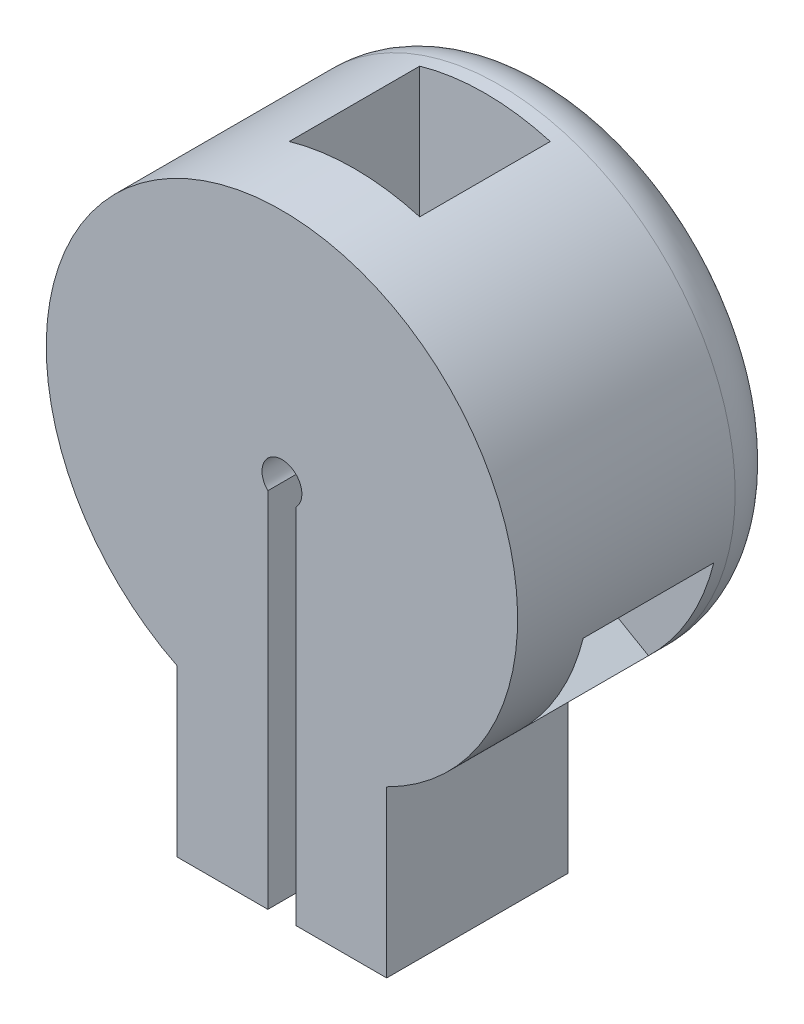
SolidWorks part; units mm, degrees
note: '?' marks a value the reader was unsure of. The reader was unsure of these and kept them because the rebuilt part matched: shared geometry of "Sketch1<4>".
ref_plane "Front Plane" through (0, 0, 0) normal (0, 0, 1) x (1, 0, 0)
ref_plane "Top Plane" through (0, 0, 0) normal (0, 1, 0) x (1, 0, 0)
ref_plane "Right Plane" through (0, 0, 0) normal (1, 0, 0) x (0, 0, -1)
sketch "Sketch1" plane through (0, 0, 0) normal (0, 0, 1) x (1, 0, 0)
  line L0 (-1.1, 0) -> (1.1, 0) construction
  line L1 (-0.7778, -20.7778) -> (-5.7778, -20.7778)
  line L2 (0, 0) -> (-0.7778, -0.7778) construction
  line L3 (-5.7778, -20.7778) -> (-5.7778, -11.6455)
  line L4 (0.7778, -20.7778) -> (5.7778, -20.7778)
  line L5 (5.7778, -20.7778) -> (5.7778, -11.6455)
  line L6 (0, 0) -> (0.7778, -0.7778) construction
  line L7 (-0.7778, -0.7778) -> (-0.7778, -20.7778)
  line L8 (0.7778, -0.7778) -> (0.7778, -20.7778)
  circle A0 centre (0, 0) radius 13
  circle A1 centre (0, 0) radius 1.1
  dimension "D1" = 2.2
  dimension "D2" = 26
  dimension "D3" = 45
  dimension "D4" = 5
  dimension "D5" = 5
  dimension "D6" = 20
  dimension "D7" = 20
extrude "Boss-Extrude1" add sketch "Sketch1" along normal blind 10 contours A1 L8 A0 L7 | A0 L3 L1 L7 | A0 L8 L4 L5
extrude "Boss-Extrude2" add sketch "Sketch1<4>" against normal blind 5 contours A1 L8 A0 L7 | A1 L7 A0 L8 | A1
sketch "Sketch1<4>" plane through (0, 0, 0) normal (0, 0, 1) x (1, 0, 0) same geometry as "Sketch1"
ref_plane "Plane1" through (0, 0, 5) normal (0, 0, -1) x (-1, 0, 0)
sketch "Sketch2" plane through (0, 0, 5) normal (0, 0, -1) x (-1, 0, 0)
  line L0 (0, 0) -> (0, -13)
  line L1 (-12.2328, 4.3999) -> (0, 0)
  line L2 (0, 0) -> (9.9268, 8.394)
  line L3 (0, 13) -> (0, -13) construction
  circle A0 centre (0, 0) radius 13 construction
  circle A1 centre (0, 0) radius 13
  dimension "D1" = 109.782
  dimension "D2" = 120
ref_plane "Plane3" through (-11.2583, -6.5, 0) normal (-0.866, -0.5, 0) x (0, 0, -1)
ref_plane "Plane2" through (0, -12.9767, 0) normal (0, -1, 0) x (-1, 0, 0)
sketch "Sketch4" plane through (-11.2864, -6.4513, 0) normal (0.866, 0.5, 0) x (0.5, -0.866, 0)
  line L0 (10.9055, 0) -> (7.2526, 0) construction
  line L1 (3.6562, 1.2) -> (-3.5438, 1.2)
  line L2 (3.6562, 1.2) -> (3.6562, -6)
  line L3 (3.6562, -6) -> (-3.5438, -6)
  line L4 (-3.5438, 1.2) -> (-3.5438, -6)
  line L5 (10.9055, 0) -> (7.2526, 0)
  line L6 (13.0562, 5) -> (-12.9438, 5) construction
  line L7 (13.0562, 5) -> (-12.9438, 5)
  line L8 (0.0562, 5) -> (0.0562, -19.3981) construction
  point P10 (0.0562, 1.2)
  dimension "D1" = 7.2
  dimension "D2" = 7.2
  dimension "D3" = 6
ref_axis "Eix de revolució" through (0, 0, 10) along (0, 0, -1)?
fillet "Fillet1" radius 3 1 edges at (13, 0, -5) type face fillet first side face at (13, 0, -5) second side face at (0, -8.0693, 3.3333)
extrude "Cut-Extrude1" cut sketch "Sketch4" along normal blind 10 contours L4 L3 L2 L1
pattern_circular "CirPattern1" count 3 over 360 about axis through (0, 0, 0) along (0, 0, 1) of "Cut-Extrude1"
hole_wizard "CSK for M3 Oval Head Machine Screw1" positions "Sketch15" profile "Sketch13" countersink size "M3" standard "ANSI Metric"
sketch "Sketch15" plane through (-5.7778, 0, 0) normal (-1, 0, 0) x (0, 0, 1)
  point P0 (6.0161, -18.3217)
sketch "Sketch13" plane through (-5.7778, -18.3217, 6.0161) normal (0, 1, 0) x (0, 0, 1)
  line L0 (0, 0) -> (0, 18.7778)
  line L1 (0, 18.7778) -> (1.8, 18.7778)
  line L2 (1.8, 18.7778) -> (1.8, 1.35)
  line L3 (1.8, 1.35) -> (3.15, 0)
  line L5 (3.15, 0) -> (0, 0)
  line L6 (-1.8, 1.35) -> (-3.15, 0) construction
  line L11 (0, -6.35) -> (0, 107.95) construction
  dimension "Thru Hole Dia." = 3.6
  dimension "Thru Hole Depth" = 18.7778
  dimension "Near C'Sink Dia." = 6.3
  dimension "Near C'Sink Angle" = 90
